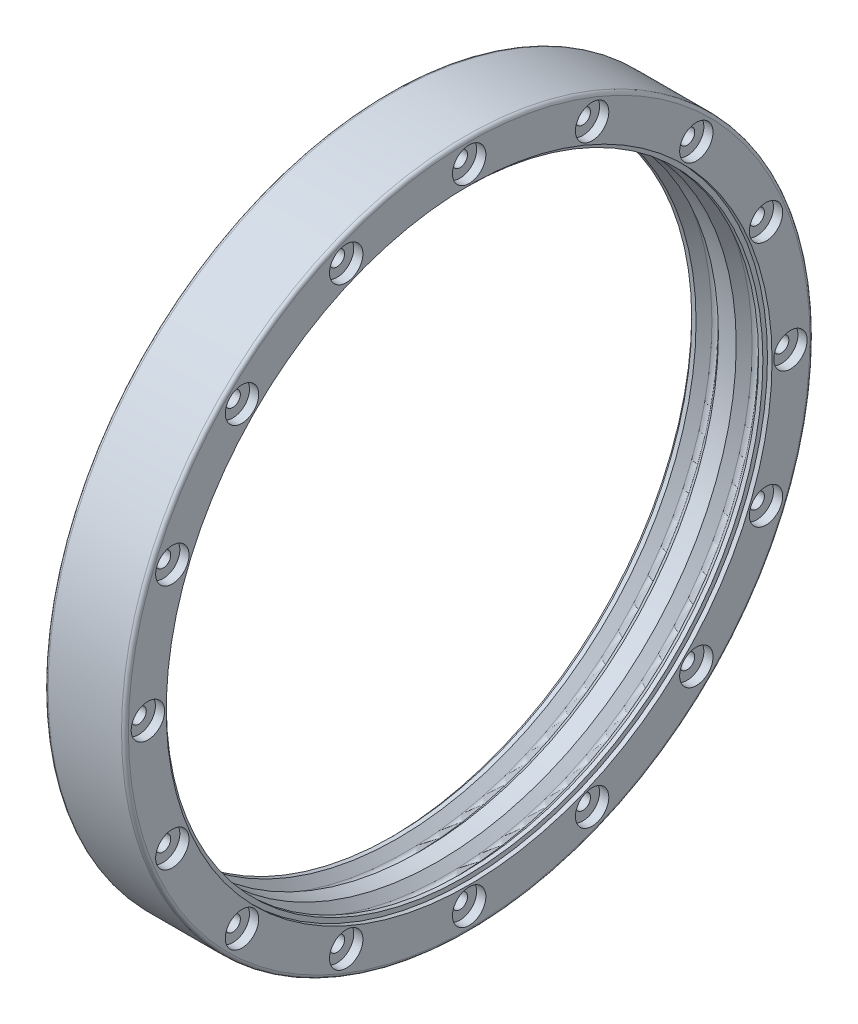
SolidWorks part; units mm, degrees
ref_plane "Front Plane" through (0, 0, 0) normal (0, 0, 1) x (1, 0, 0)
ref_plane "Top Plane" through (0, 0, 0) normal (0, 1, 0) x (1, 0, 0)
ref_plane "Right Plane" through (0, 0, 0) normal (1, 0, 0) x (0, 0, -1)
sketch "Sketch1" plane through (0, 0, 0) normal (0, 0, 1) x (1, 0, 0)
  line L5 (-17.5, 150) -> (17.5, 150)
  line L6 (17.5, 150) -> (17.5, 130)
  line L7 (17.5, 130) -> (-17.5, 130)
  line L8 (-17.5, 130) -> (-17.5, 150)
  line L9 (0, 150) -> (0, 0) construction
  line L18 (-17.5, 140) -> (0, 140) construction
  line L19 (-8.75, 134.864) -> (-2.386, 128.5)
  line L20 (0, 0) -> (-48.8175, 0) construction
  line L21 (-8.75, 134.864) -> (-15.114, 128.5)
  line L22 (-8.75, 140) -> (-8.75, 0) construction
  line L23 (-2.386, 128.5) -> (-8.75, 122.136)
  line L24 (-15.114, 128.5) -> (-8.75, 122.136)
  line L25 (-8.75, 134.864) -> (-8.75, 122.136) construction
  line L26 (-2.386, 128.5) -> (-15.114, 128.5) construction
  line L27 (2.386, 128.5) -> (8.75, 122.136)
  line L28 (15.114, 128.5) -> (8.75, 122.136)
  line L29 (8.75, 134.864) -> (15.114, 128.5)
  line L30 (8.75, 134.864) -> (2.386, 128.5)
  point P11 (-8.75, 128.5)
  dimension "D1" = 35
  dimension "D2" = 150
  dimension "D3" = 130
  dimension "D4" = 1.5
  dimension "D5" = 9
revolve "Revolve1" add sketch "Sketch1" angle 360 about L20 region at (0, 140.6074, 0)
ref_axis "Axis1" through (-17.5, 0, 0) along (1, 0, 0)
fillet "Fillet1" radius 2 2 edges at (8.75, 0, -134.864) (-8.75, 0, -134.864)
ref_plane "Plane1" through (0, 128.5, 0) normal (0, 1, 0) x (1, 0, 0)
ref_axis "Axis2" through (19.25, 128.5, 0) along (-1, 0, 0)
ref_plane "Plane2" through (-8.75, 0, 0) normal (1, 0, 0) x (0, 0, -1)
sketch "Sketch2" plane through (17.5, 0, 0) normal (1, 0, 0) x (0, 0, -1)
  line L0 (150, 0) -> (130, 0) construction
  circle A0 centre (0, 0) radius 150 construction
  circle A1 centre (0, 0) radius 130 construction
  point P8 (140, 0)
hole_wizard "CBORE for M6 Hex Head Bolt1" positions "3DSketch3" profile "Sketch3" counterbore size "M6" standard "ISO" end condition through all
sketch3d "3DSketch3"
  point P0 (17.5, 0, -140)
sketch "Sketch3" plane through (17.5, 0, -140) normal (0, 1, 0) x (0, 0, -1)
  line L0 (0, 0) -> (0, 35)
  line L1 (0, 35) -> (3.3, 35)
  line L3 (3.3, 35) -> (3.3, 4)
  line L4 (3.3, 4) -> (7.2735, 4)
  line L5 (7.2735, 4) -> (7.2735, 0)
  line L7 (7.2735, 0) -> (0, 0)
  line L11 (0, -6.35) -> (0, 107.95) construction
  dimension "Thru Hole Dia." = 6.6
  dimension "Thru Hole Depth" = 35
  dimension "C'Bore Dia." = 14.547
  dimension "C'Bore Depth" = 4
pattern_circular "CirPattern1" count 16 over 360 about axis through (-17.5, 0, 0) along (1, 0, 0) of "CBORE for M6 Hex Head Bolt1"
fillet "Fillet2" radius 1.5 2 edges at (-17.5, 0, -150) (17.5, 0, -150)
sketch "Sketch4" plane through (17.5, 0, 0) normal (1, 0, 0) x (0, 0, -1)
  circle A0 centre (0, 0) radius 130 construction
  circle A1 centre (0, 0) radius 130
  circle A2 centre (0, 0) radius 132
  dimension "D1" = 2
extrude "Cut-Extrude1" cut sketch "Sketch4" against normal blind 2
mirror "Mirror1" about plane through (0, 0, 0) normal (1, 0, 0) of "Cut-Extrude1"
